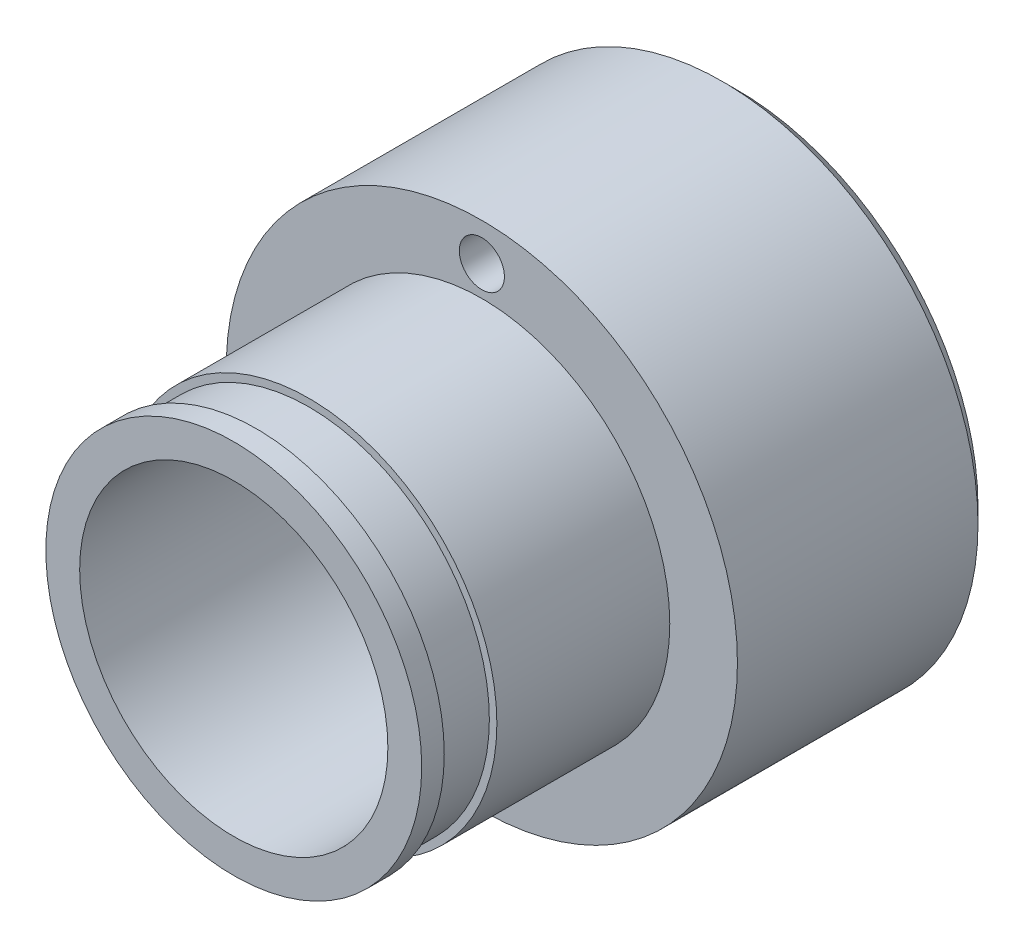
SolidWorks part; units mm, degrees
material "Porcelaine céramique"
ref_plane "Plan de face" through (0, 0, 0) normal (0, 0, 1) x (1, 0, 0)
ref_plane "Plan de dessus" through (0, 0, 0) normal (0, 1, 0) x (1, 0, 0)
ref_plane "Plan de droite" through (0, 0, 0) normal (1, 0, 0) x (0, 0, -1)
sketch "Esquisse1" plane through (0, 0, 0) normal (0, 0, 1) x (1, 0, 0)
  circle A0 centre (0, 0) radius 17
  dimension "D1" = 34
extrude "Boss.-Extru.1" add sketch "Esquisse1" along normal blind 17
sketch "Esquisse2" plane through (0, 0, 17) normal (0, 0, 1) x (1, 0, 0)
  circle A0 centre (0, 0) radius 12.5
  dimension "D1" = 25
extrude "Boss.-Extru.2" add sketch "Esquisse2" along normal blind 11.5
sketch "Esquisse3" plane through (0, 0, 28.5) normal (0, 0, 1) x (1, 0, 0)
  circle A0 centre (0, 0) radius 12
  dimension "D1" = 24
extrude "Boss.-Extru.3" add sketch "Esquisse3" along normal blind 3.5
sketch "Esquisse4" plane through (0, 0, 32) normal (0, 0, 1) x (1, 0, 0)
  circle A0 centre (0, 0) radius 12.5
  dimension "D1" = 25
extrude "Boss.-Extru.4" add sketch "Esquisse4" along normal blind 1.5
sketch "Esquisse5" plane through (0, 0, 33.5) normal (0, 0, 1) x (1, 0, 0)
  circle A0 centre (0, 0) radius 10.25
  dimension "D1" = 20.5
extrude "Enlèv. mat.-Extru.1" cut sketch "Esquisse5" against normal blind 30
cosmetic thread "Représentation de filetage1" parameters "D1"=28, "D2"=21.5
sketch "Esquisse6" plane through (0, 0, 3.5) normal (0, 0, 1) x (1, 0, 0)
  circle A0 centre (0, 0) radius 10.25
  circle A1 centre (0, 0) radius 6.75
  dimension "D1" = 20.5
  dimension "D2" = 13.5
extrude "Enlèv. mat.-Extru.2" cut sketch "Esquisse6" against normal blind 1.5
sketch "Esquisse7" plane through (0, 0, 3.5) normal (0, 0, 1) x (1, 0, 0)
  circle A0 centre (0, 0) radius 12
  circle A1 centre (0, 0) radius 10.25
  dimension "D1" = 24
  dimension "D2" = 20.5
extrude "Enlèv. mat.-Extru.3" cut sketch "Esquisse7" along normal blind 2
hole_wizard "Diamètre du perçage Ø3.0 (3)1" positions "Esquisse9" profile "Esquisse8" hole size "Ø3.0" standard "ISO"
sketch "Esquisse9" plane through (0, 0, 17) normal (0, 0, 1) x (1, 0, 0)
  line L0 (0, 0) -> (0, 14.5) construction
  point P5 (0, 14.5)
  point P10 (0, 14.5)
  dimension "D1" = 14.5
sketch "Esquisse8" plane through (0, 14.5, 17) normal (1, 0, 0) x (0, -1, 0)
  line L0 (0, 0) -> (0, 12.9013)
  line L1 (0, 12.9013) -> (1.5, 12)
  line L2 (1.5, 12) -> (1.5, 0)
  line L5 (1.5, 0) -> (0, 0)
  line L10 (0, 12.9013) -> (-1.5, 12) construction
  line L11 (0, -6.35) -> (0, 107.95) construction
  dimension "Diamètre du perçage" = 3
  dimension "Profondeur du perçage" = 12
  dimension "Angle de pointe" = 118
chamfer "Chanfrein1" distance 1 angle 45 1 edges at (17, 0, 0)
